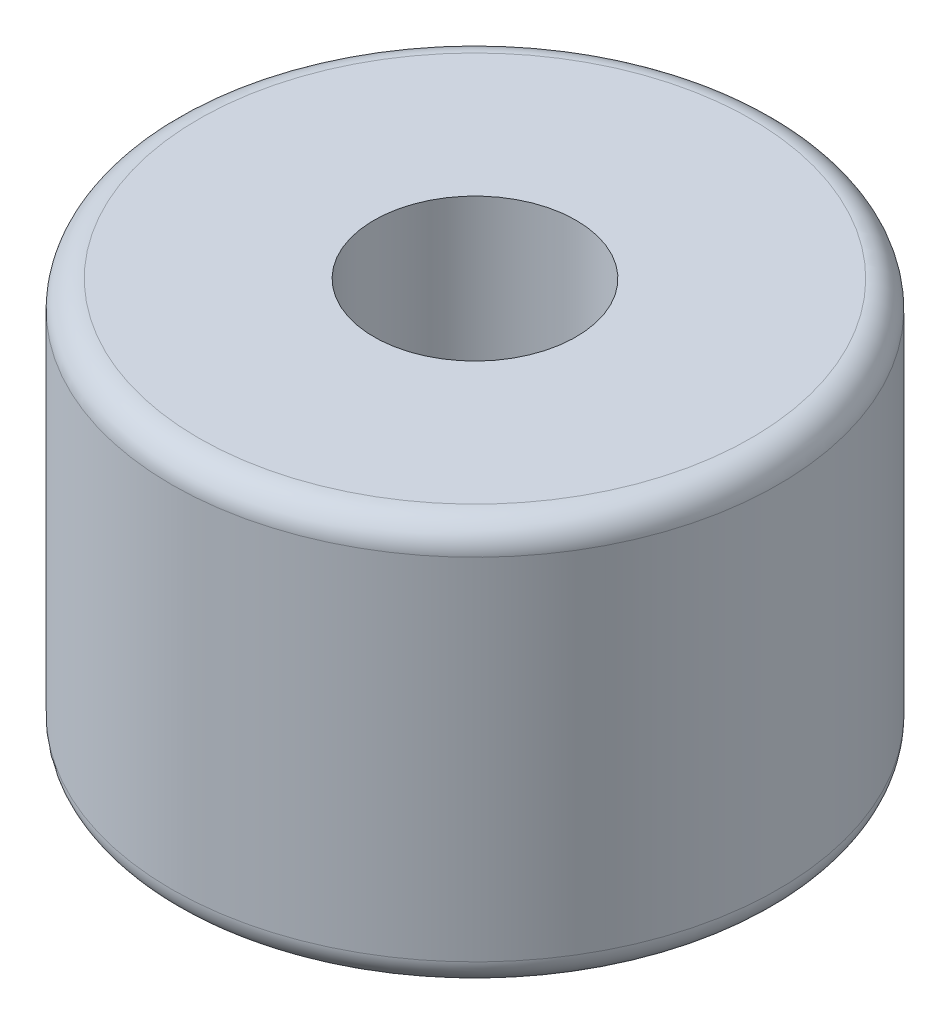
SolidWorks part; units mm, degrees
ref_plane "Front Plane" through (0, 0, 0) normal (0, 0, 1) x (1, 0, 0)
ref_plane "Top Plane" through (0, 0, 0) normal (0, 1, 0) x (1, 0, 0)
ref_plane "Right Plane" through (0, 0, 0) normal (1, 0, 0) x (0, 0, -1)
sketch "Sketch2" plane through (0, 0, 0) normal (0, 0, 1) x (1, 0, 0)
  line L0 (0, 0) -> (0, 9.525) construction
  line L1 (2.3813, 0) -> (7.1437, 0)
  line L2 (2.3813, 0) -> (2.3813, 9.525)
  line L3 (2.3813, 9.525) -> (7.1437, 9.525)
  line L4 (7.1437, 0) -> (7.1437, 9.525)
  dimension "D1" = 7.1437
  dimension "D2" = 2.3813
  dimension "D3" = 9.525
revolve "Revolve1" add sketch "Sketch2" angle 360 about L0
fillet "Fillet1" radius 0.635 2 edges at (0, 0, -7.1437) (0, 9.525, -7.1437)
